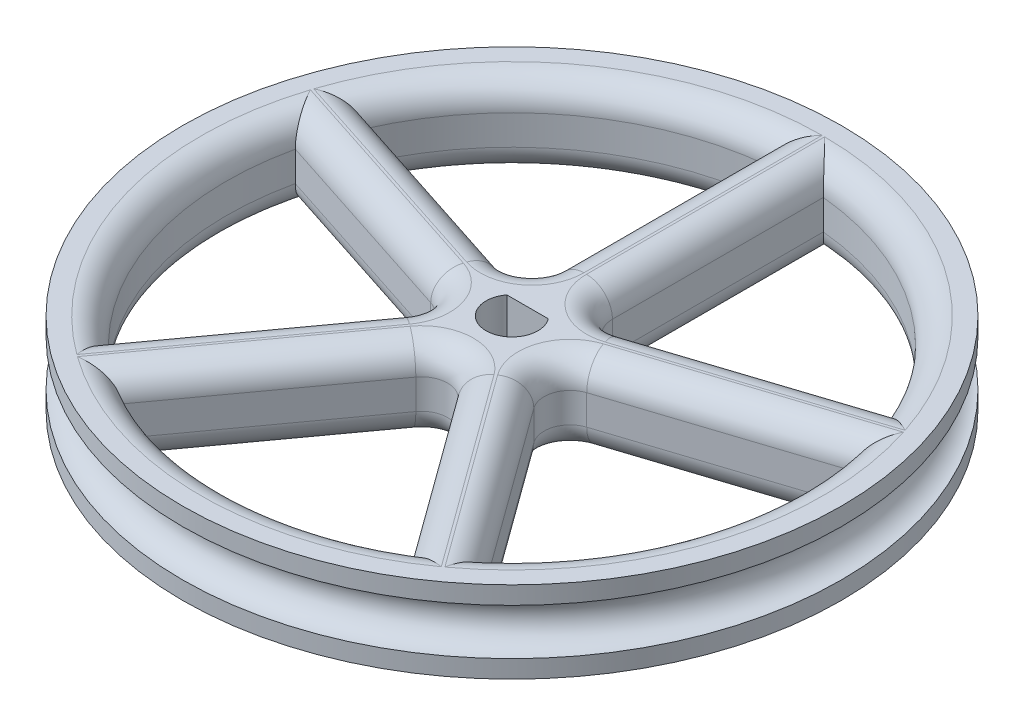
SolidWorks part; units mm, degrees
ref_plane "정면" through (0, 0, 0) normal (0, 0, 1) x (1, 0, 0)
ref_plane "윗면" through (0, 0, 0) normal (0, 1, 0) x (1, 0, 0)
ref_plane "우측면" through (0, 0, 0) normal (1, 0, 0) x (0, 0, -1)
sketch "Sketch1" plane through (0, 0, 0) normal (0, 1, 0) x (1, 0, 0)
  line L0 (0, 1.2) -> (-1.6, 1.2)
  line L1 (0, 1.2) -> (1.6, 1.2)
  line L2 (-2.0991, 5.6419) -> (-2.0991, 21.8996)
  line L3 (2.0991, 5.6419) -> (2.0991, 21.8996)
  line L4 (4.7171, 3.7398) -> (20.1791, 8.7637)
  line L5 (6.0145, -0.2529) -> (21.4764, 4.771)
  line L6 (5.0145, -3.3306) -> (14.5705, -16.4833)
  line L7 (1.618, -5.7982) -> (11.1741, -18.951)
  line L8 (-1.618, -5.7982) -> (-11.1741, -18.951)
  line L9 (-5.0145, -3.3306) -> (-14.5705, -16.4833)
  line L10 (-4.7171, 3.7398) -> (-20.1791, 8.7637)
  line L11 (-6.0145, -0.2529) -> (-21.4764, 4.771)
  circle A0 centre (0, 0) radius 25.4
  arc A1 (-1.6, 1.2) -> (1.6, 1.2) centre (0, 0) ccw
  arc A2 (-2.0991, 21.8996) -> (-20.1791, 8.7637) centre (0, 0) ccw
  arc A3 (-2.0991, 5.6419) -> (-4.7171, 3.7398) centre (-4.0991, 5.6419) cw
  arc A4 (-21.4764, 4.771) -> (-14.5705, -16.4833) centre (0, 0) ccw
  arc A5 (-11.1741, -18.951) -> (11.1741, -18.951) centre (0, 0) ccw
  arc A6 (14.5705, -16.4833) -> (21.4764, 4.771) centre (0, 0) ccw
  arc A7 (20.1791, 8.7637) -> (2.0991, 21.8996) centre (0, 0) ccw
  arc A8 (-6.0145, -0.2529) -> (-5.0145, -3.3306) centre (-6.6325, -2.155) cw
  arc A9 (-1.618, -5.7982) -> (1.618, -5.7982) centre (0, -6.9738) cw
  arc A10 (5.0145, -3.3306) -> (6.0145, -0.2529) centre (6.6325, -2.155) cw
  arc A11 (4.7171, 3.7398) -> (2.0991, 5.6419) centre (4.0991, 5.6419) cw
  dimension "D1" = 2
  dimension "D2" = 2
extrude "Boss-Extrude1" add sketch "Sketch1" along normal blind 6.3
sketch "Sketch3" plane through (0, 0, 0) normal (-0.5658, 0, 0.8246) x (0.8246, 0, 0.5658)
  line L0 (0, 71.7523) -> (0, 0) construction
  line L1 (0, 0) -> (0, 4.928) construction
  line L2 (0, 3.15) -> (25.4, 3.15) construction
  line L3 (12.7, 3.15) -> (12.7, -2.0543) construction
  circle A1 centre (25.4, 3.15) radius 1.778
revolve "Cut-Revolve3" cut sketch "Sketch3" angle 360 about L0
fillet "Fillet1" radius 2 40 edges at (6.396, 0, 12.3746) (-6.396, 0, 12.3746) (0, 0, 4.9738) (-9.7925, 0, 9.907) (-20.9232, 0, 6.7984) (-13.7455, 0, -2.259) (-4.7304, 0, 1.537) (-12.4481, 0, -6.2518) (-12.9313, 0, -17.7984) (-2.0991, 0, -13.7708) (-2.9235, 0, -4.0239) (12.4481, 0, -6.2518) (2.9235, 0, -4.0239) (2.0991, 0, -13.7708) (12.9313, 0, -17.7984) (9.7925, 0, 9.907) (4.7304, 0, 1.537) (13.7455, 0, -2.259) (20.9232, 0, 6.7984) (0, 0, 22) (6.396, 6.3, 12.3746) (0, 6.3, 4.9738) (-6.396, 6.3, 12.3746) (-20.9232, 6.3, 6.7984) (-9.7925, 6.3, 9.907) (-4.7304, 6.3, 1.537) (-13.7455, 6.3, -2.259) (-12.9313, 6.3, -17.7984) (-12.4481, 6.3, -6.2518) (-2.9235, 6.3, -4.0239) (-2.0991, 6.3, -13.7708) (2.9235, 6.3, -4.0239) (12.4481, 6.3, -6.2518) (12.9313, 6.3, -17.7984) (2.0991, 6.3, -13.7708) (4.7304, 6.3, 1.537) (9.7925, 6.3, 9.907) (20.9232, 6.3, 6.7984) (13.7455, 6.3, -2.259) (0, 6.3, 22)
